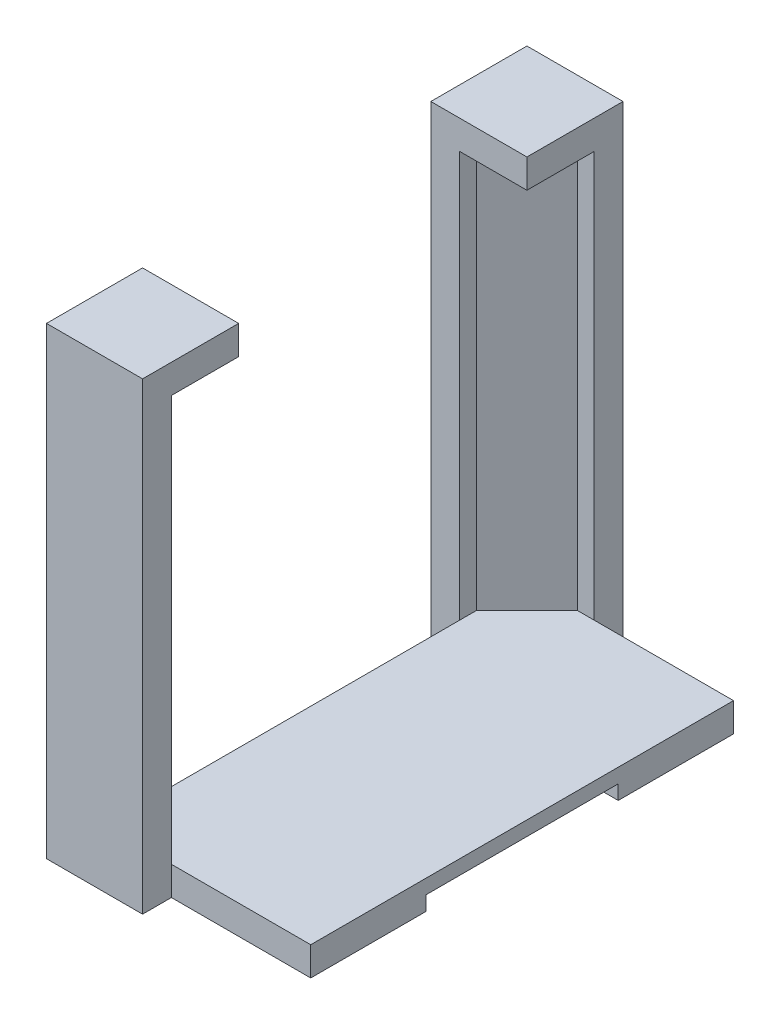
SolidWorks part; units mm, degrees
ref_plane "Front Plane" through (0, 0, 0) normal (0, 0, 1) x (1, 0, 0)
ref_plane "Top Plane" through (0, 0, 0) normal (0, 1, 0) x (1, 0, 0)
ref_plane "Right Plane" through (0, 0, 0) normal (1, 0, 0) x (0, 0, -1)
sketch "Sketch1" plane through (0, 0, 0) normal (0, 1, 0) x (1, 0, 0)
  line L0 (-21.5, 37) -> (-24.5, 37)
  line L1 (0, 0) -> (-21.5, 0)
  line L2 (0, 0) -> (0, 44)
  line L3 (0, 44) -> (-21.5, 44)
  line L4 (-21.5, 0) -> (-21.5, 44)
  line L5 (-24.5, 37) -> (-24.5, 47)
  line L6 (-24.5, 47) -> (-14.5, 47)
  line L7 (-14.5, 47) -> (-14.5, 44)
  line L8 (-21.5, 22) -> (0, 22) construction
  line L9 (-24.5, 7) -> (-24.5, -3)
  line L10 (-21.5, 7) -> (-24.5, 7)
  line L11 (-14.5, -3) -> (-14.5, 0)
  line L12 (-24.5, -3) -> (-14.5, -3)
  line L13 (0, 32) -> (-10, 32)
  line L14 (-10, 32) -> (-10, 12)
  line L15 (-10, 12) -> (0, 12)
  point P19 (-10, 22)
  dimension "D1" = 21.5
  dimension "D2" = 44
  dimension "D3" = 3
  dimension "D4" = 20
  dimension "D5" = 10
  dimension "D6" = 10
  dimension "D7" = 10
extrude "Boss-Extrude2" add sketch "Sketch1" along normal blind 3 contours L4 L8 L14 L13 L2 L3 | L8 L4 L1 L2 L15 L14 | L14 L8 L2 L13 | L8 L14 L15 L2 region at (-12.2916, 0, -34.6086) region at (-12.2916, 0, -9.3914) region at (-5, 0, -27) region at (-5, 0, -17)
extrude "Cut-Extrude1" cut sketch "Sketch1<8>" along normal blind 1.5 contours L8 L14 L15 L2 | L14 L8 L2 L13 region at (-5, 0, -27) region at (-5, 0, -17)
sketch "Sketch1<8>" plane through (0, 0, 0) normal (0, 1, 0) x (1, 0, 0) same geometry as "Sketch1"
extrude "Boss-Extrude3" add sketch "Sketch1<9>" along normal blind 45.25 contours L9 L12 L11 L1 L4 L10 | L7 L6 L5 L0 L4 L3 region at (-23, 0, -37.1414) region at (-21.6414, 0, -3.5)
sketch "Sketch1<9>" plane through (0, 0, 0) normal (0, 1, 0) x (1, 0, 0) same geometry as "Sketch1"
sketch "Sketch2" plane through (0, 45.25, 0) normal (0, 1, 0) x (1, 0, 0)
  line L1 (-24.5, -3) -> (-14.5, -3)
  line L2 (-24.5, -3) -> (-24.5, 7)
  line L3 (-24.5, 7) -> (-14.5, 7)
  line L4 (-14.5, -3) -> (-14.5, 7)
  line L5 (-21.5, 7) -> (-21.5, 37) construction
  line L6 (-21.5, 22) -> (0, 22) construction
  line L7 (0, 0) -> (0, 44) construction
  line L8 (-24.5, 47) -> (-24.5, 37)
  line L9 (-24.5, 47) -> (-14.5, 47)
  line L10 (-14.5, 47) -> (-14.5, 37)
  line L11 (-24.5, 37) -> (-14.5, 37)
extrude "Boss-Extrude4" add sketch "Sketch2" along normal blind 3
chamfer "Chamfer4" distance 5.25 angle 45 2 edges at (-21.5, 24.125, 0) (-21.5, 24.125, -44)
